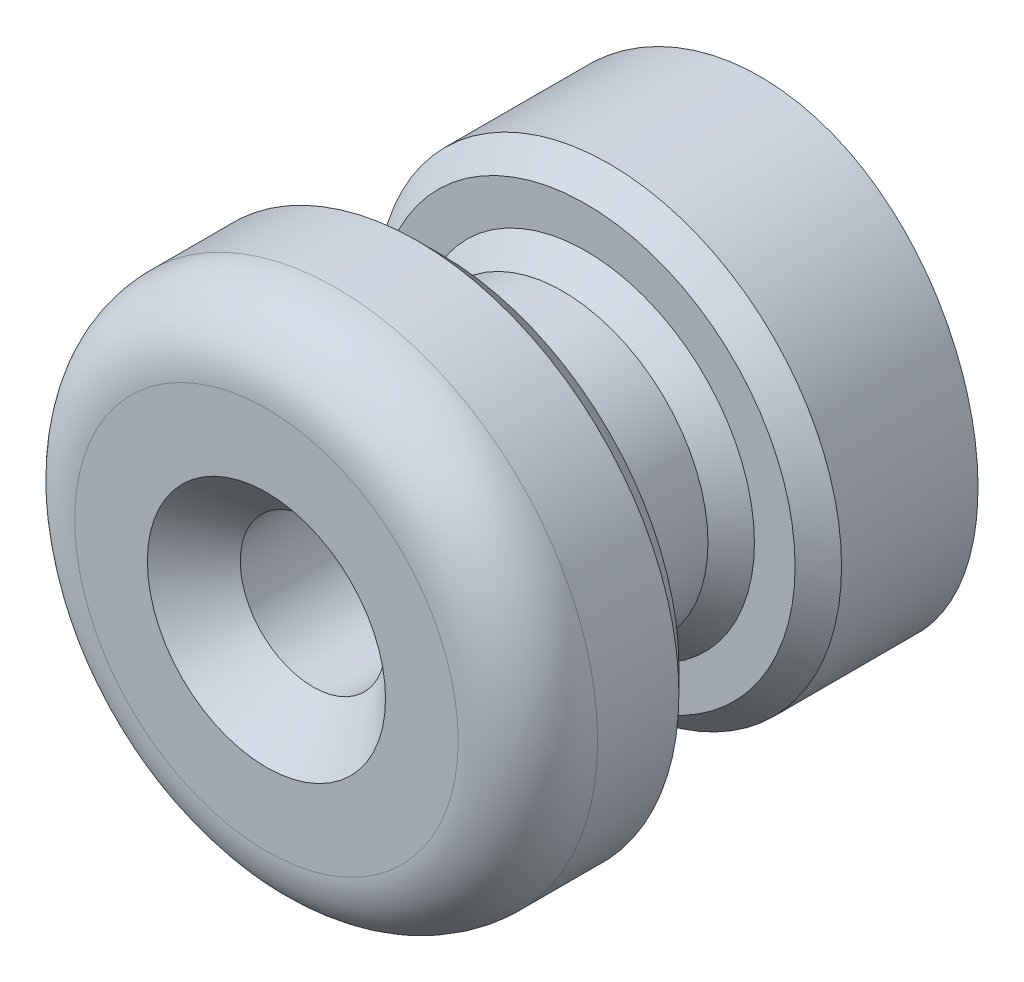
SolidWorks part; units mm, degrees
ref_plane "Front Plane" through (0, 0, 0) normal (0, 0, 1) x (1, 0, 0)
ref_plane "Top Plane" through (0, 0, 0) normal (0, 1, 0) x (1, 0, 0)
ref_plane "Right Plane" through (0, 0, 0) normal (1, 0, 0) x (0, 0, -1)
sketch "Sketch1" plane through (0, 0, 0) normal (0, 0, 1) x (1, 0, 0)
  circle A0 centre (0, 0) radius 5.08
  circle A1 centre (0, 0) radius 1.5875
  dimension "D1" = 10.16
  dimension "D2" = 3.175
extrude "Boss-Extrude1" add sketch "Sketch1" along normal blind 3.81
sketch "Sketch2" plane through (0, 0, 3.81) normal (0, 0, 1) x (1, 0, 0)
  circle A0 centre (0, 0) radius 1.5875
  circle A1 centre (0, 0) radius 3.175
  dimension "D1" = 6.35
  dimension "D2" = 3.175
extrude "Boss-Extrude2" add sketch "Sketch2" along normal blind 3.175
sketch "Sketch3" plane through (0, 0, 6.985) normal (0, 0, 1) x (1, 0, 0)
  circle A0 centre (0, 0) radius 1.5875
  circle A1 centre (0, 0) radius 5.715
  circle A2 centre (0, 0) radius 1.5875 construction
  dimension "D1" = 11.43
extrude "Boss-Extrude3" add sketch "Sketch3" along normal blind 3.81
chamfer "Chamfer1" distance 0.508 angle 45 2 edges at (3.175, 0, 3.81) (3.175, 0, 6.985)
chamfer "Chamfer2" distance 0.508 angle 45 2 edges at (5.08, 0, 3.81) (5.715, 0, 6.985)
fillet "Fillet1" radius 1.524 1 edges at (5.715, 0, 10.795)
chamfer "Chamfer3" distance 1.016 angle 45 1 edges at (1.5875, 0, 10.795)
sketch "Sketch4" plane through (0, 0, 0) normal (1, 0, 0) x (0, 0, -1)
  circle A0 centre (40.3212, 0) radius 40.64
  point P2 (0, 0)
  dimension "D1" = 81.28
extrude "Cut-Extrude1" cut sketch "Sketch4" against normal through all both and the other way through all
